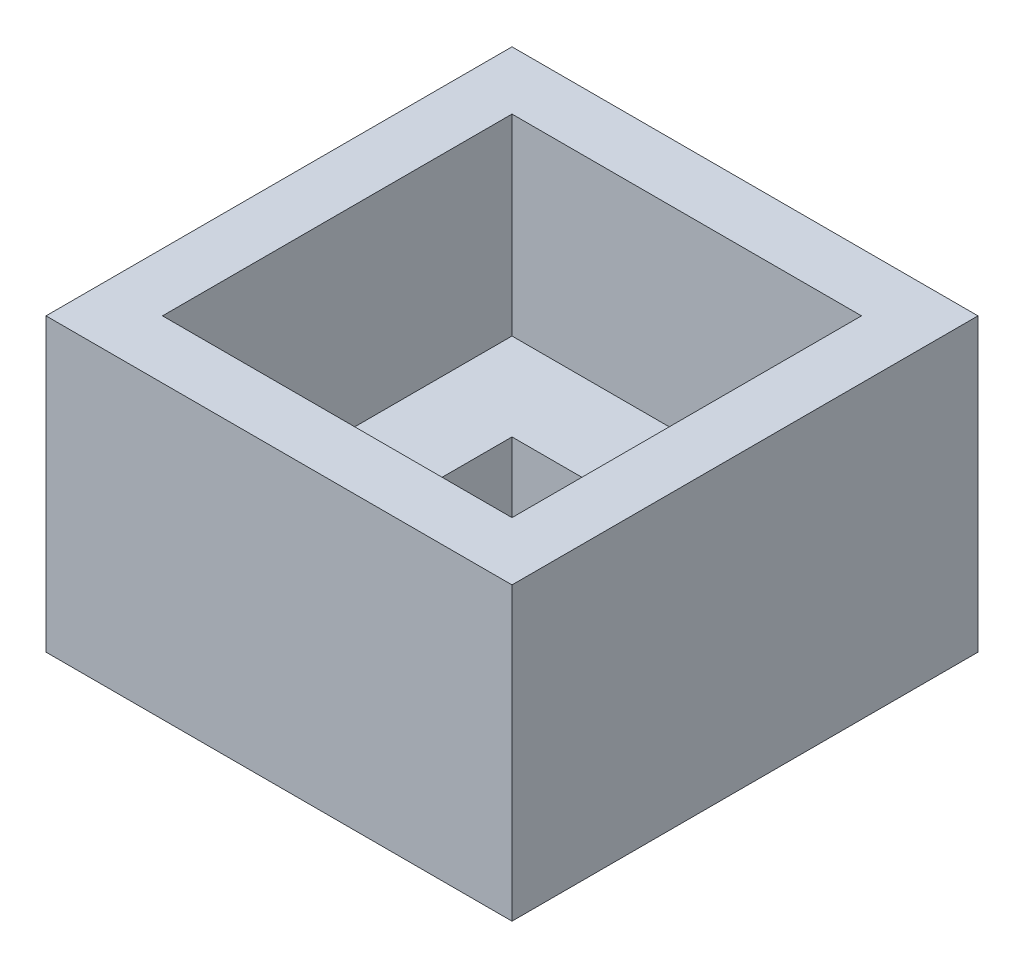
SolidWorks part; units mm, degrees
material "Polyurethane Foam Rigid"
ref_plane "Front Plane" through (0, 0, 0) normal (0, 0, 1) x (1, 0, 0)
ref_plane "Top Plane" through (0, 0, 0) normal (0, 1, 0) x (1, 0, 0)
ref_plane "Right Plane" through (0, 0, 0) normal (1, 0, 0) x (0, 0, -1)
sketch "Sketch1" plane through (0, 0, 0) normal (0, 1, 0) x (1, 0, 0)
  line L1 (-50.8, -50.8) -> (50.8, -50.8)
  line L2 (-50.8, -50.8) -> (-50.8, 50.8)
  line L3 (-50.8, 50.8) -> (50.8, 50.8)
  line L4 (50.8, -50.8) -> (50.8, 50.8)
  line L5 (-50.8, -50.8) -> (50.8, 50.8) construction
  line L6 (-50.8, 50.8) -> (50.8, -50.8) construction
  line L7 (-19.05, -19.05) -> (19.05, -19.05)
  line L8 (-19.05, -19.05) -> (-19.05, 19.05)
  line L9 (-19.05, 19.05) -> (19.05, 19.05)
  line L10 (19.05, -19.05) -> (19.05, 19.05)
  line L11 (-19.05, -19.05) -> (19.05, 19.05) construction
  line L12 (-19.05, 19.05) -> (19.05, -19.05) construction
  point P0 (0, 0)
  point P6 (0, 0)
  dimension "D1" = 101.6
  dimension "D2" = 101.6
  dimension "D3" = 38.1
  dimension "D4" = 38.1
extrude "Boss-Extrude1" add sketch "Sketch1" along normal blind 76.2
sketch "Sketch3" plane through (0, 76.2, 0) normal (0, 1, 0) x (1, 0, 0)
  line L1 (-38.1, -38.1) -> (38.1, -38.1)
  line L2 (-38.1, -38.1) -> (-38.1, 38.1)
  line L3 (-38.1, 38.1) -> (38.1, 38.1)
  line L4 (38.1, -38.1) -> (38.1, 38.1)
  line L5 (-38.1, -38.1) -> (38.1, 38.1) construction
  line L6 (-38.1, 38.1) -> (38.1, -38.1) construction
  point P0 (0, 0)
  dimension "D1" = 76.2
  dimension "D2" = 76.2
extrude "Cut-Extrude2" cut sketch "Sketch3" against normal blind 54.61
sketch "Sketch5" plane through (0, 76.2, 0) normal (0, 1, 0) x (1, 0, 0)
  line L1 (-38.1, -38.1) -> (38.1, -38.1)
  line L2 (-38.1, -38.1) -> (-38.1, 38.1)
  line L3 (-38.1, 38.1) -> (38.1, 38.1)
  line L4 (38.1, -38.1) -> (38.1, 38.1)
  line L5 (-38.1, -38.1) -> (38.1, 38.1) construction
  line L6 (-38.1, 38.1) -> (38.1, -38.1) construction
  line L7 (-50.8, -50.8) -> (50.8, -50.8)
  line L8 (-50.8, -50.8) -> (-50.8, 50.8)
  line L9 (-50.8, 50.8) -> (50.8, 50.8)
  line L10 (50.8, -50.8) -> (50.8, 50.8)
  line L11 (-50.8, -50.8) -> (50.8, 50.8) construction
  line L12 (-50.8, 50.8) -> (50.8, -50.8) construction
  point P0 (0, 0)
  point P7 (0, 0)
extrude "Cut-Extrude3" cut sketch "Sketch5" against normal blind 12.7
